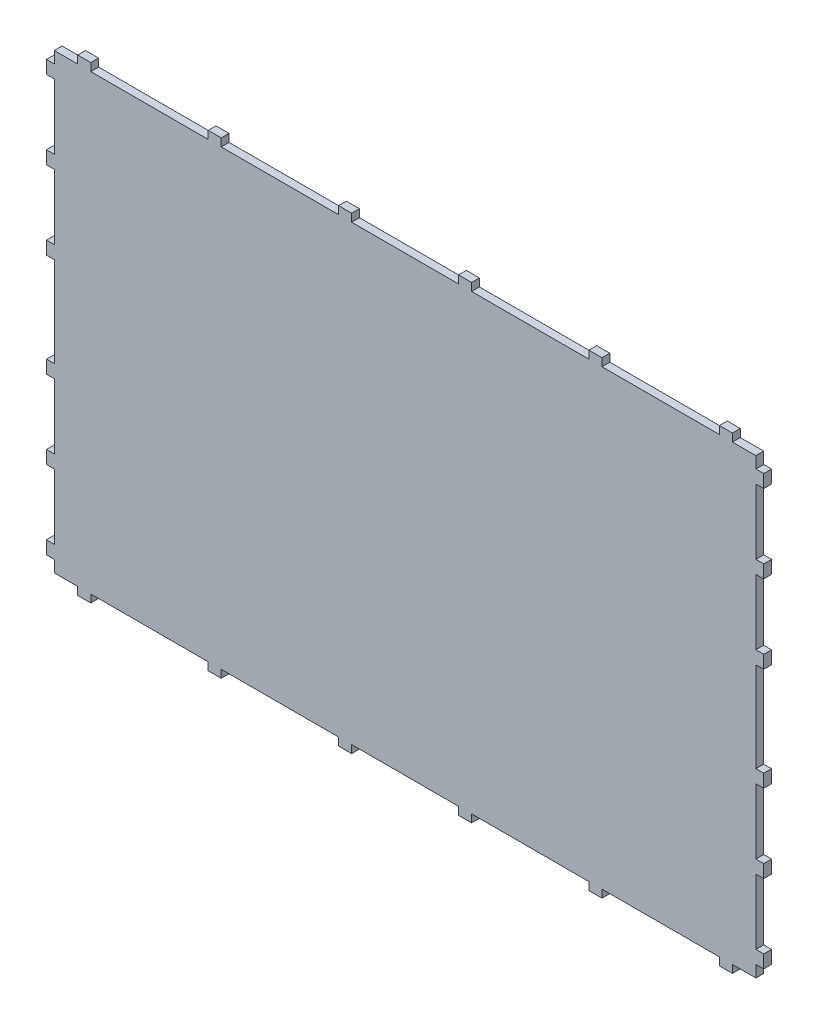
SolidWorks part; units mm, degrees
material "Клен"
ref_plane "Спереди" through (0, 0, 0) normal (0, 0, 1) x (1, 0, 0)
ref_plane "Сверху" through (0, 0, 0) normal (0, 1, 0) x (1, 0, 0)
ref_plane "Справа" through (0, 0, 0) normal (1, 0, 0) x (0, 0, -1)
sketch "Эскиз1" plane through (0, 0, 0) normal (0, 0, 1) x (1, 0, 0)
  line L0 (-367.4727, 191.9298) -> (-349.4727, 191.9298)
  line L1 (-367.4727, 191.9298) -> (-367.4727, 183.0298)
  line L2 (-367.4727, -154.9702) -> (-349.4727, -154.9702)
  line L3 (170.5273, 191.9298) -> (170.5273, 183.0298)
  line L4 (-339.4727, -154.9702) -> (-339.4727, -160.9702) construction
  line L5 (-373.4727, 183.0298) -> (-367.4727, 183.0298)
  line L6 (-373.4727, 183.0298) -> (-373.4727, 173.0298)
  line L7 (-373.4727, 173.0298) -> (-367.4727, 173.0298)
  line L9 (-349.4727, 197.9298) -> (-339.4727, 197.9298)
  line L10 (-349.4727, 197.9298) -> (-349.4727, 191.9298)
  line L12 (-339.4727, 197.9298) -> (-339.4727, 191.9298)
  line L13 (-249.4727, 197.9298) -> (-239.4727, 197.9298)
  line L14 (-249.4727, 197.9298) -> (-249.4727, 191.9298)
  line L16 (-239.4727, 197.9298) -> (-239.4727, 191.9298)
  line L18 (-149.4727, 191.9298) -> (-149.4727, 197.9298)
  line L19 (-149.4727, 197.9298) -> (-139.4727, 197.9298)
  line L20 (-139.4727, 191.9298) -> (-139.4727, 197.9298)
  line L22 (-57.4727, 191.9298) -> (-57.4727, 197.9298)
  line L23 (-57.4727, 197.9298) -> (-47.4727, 197.9298)
  line L24 (-47.4727, 191.9298) -> (-47.4727, 197.9298)
  line L26 (42.5273, 191.9298) -> (42.5273, 197.9298)
  line L27 (42.5273, 197.9298) -> (52.5273, 197.9298)
  line L28 (52.5273, 191.9298) -> (52.5273, 197.9298)
  line L30 (142.5273, 191.9298) -> (142.5273, 197.9298)
  line L31 (142.5273, 197.9298) -> (152.5273, 197.9298)
  line L32 (152.5273, 191.9298) -> (152.5273, 197.9298)
  line L33 (170.5273, 183.0298) -> (176.5273, 183.0298)
  line L35 (170.5273, 173.0298) -> (176.5273, 173.0298)
  line L36 (176.5273, 183.0298) -> (176.5273, 173.0298)
  line L37 (170.5273, 123.0298) -> (176.5273, 123.0298)
  line L39 (170.5273, 113.0298) -> (176.5273, 113.0298)
  line L40 (176.5273, 123.0298) -> (176.5273, 113.0298)
  line L41 (170.5273, 63.0298) -> (176.5273, 63.0298)
  line L43 (170.5273, 53.0298) -> (176.5273, 53.0298)
  line L44 (176.5273, 63.0298) -> (176.5273, 53.0298)
  line L45 (170.5273, -15.9702) -> (176.5273, -15.9702)
  line L47 (170.5273, -25.9702) -> (176.5273, -25.9702)
  line L48 (176.5273, -15.9702) -> (176.5273, -25.9702)
  line L49 (170.5273, -75.9702) -> (176.5273, -75.9702)
  line L51 (170.5273, -85.9702) -> (176.5273, -85.9702)
  line L52 (176.5273, -75.9702) -> (176.5273, -85.9702)
  line L53 (170.5273, -135.9702) -> (176.5273, -135.9702)
  line L55 (170.5273, -145.9702) -> (176.5273, -145.9702)
  line L56 (176.5273, -135.9702) -> (176.5273, -145.9702)
  line L58 (142.5273, -154.9702) -> (142.5273, -160.9702)
  line L59 (142.5273, -160.9702) -> (152.5273, -160.9702)
  line L60 (152.5273, -154.9702) -> (152.5273, -160.9702)
  line L62 (42.5273, -154.9702) -> (42.5273, -160.9702)
  line L63 (42.5273, -160.9702) -> (52.5273, -160.9702)
  line L64 (52.5273, -154.9702) -> (52.5273, -160.9702)
  line L66 (-57.4727, -154.9702) -> (-57.4727, -160.9702)
  line L67 (-57.4727, -160.9702) -> (-47.4727, -160.9702)
  line L68 (-47.4727, -154.9702) -> (-47.4727, -160.9702)
  line L70 (-149.4727, -154.9702) -> (-149.4727, -160.9702)
  line L71 (-149.4727, -160.9702) -> (-139.4727, -160.9702)
  line L72 (-139.4727, -154.9702) -> (-139.4727, -160.9702)
  line L74 (-249.4727, -154.9702) -> (-249.4727, -160.9702)
  line L75 (-249.4727, -160.9702) -> (-239.4727, -160.9702)
  line L76 (-239.4727, -154.9702) -> (-239.4727, -160.9702)
  line L78 (-349.4727, -154.9702) -> (-349.4727, -160.9702)
  line L79 (-349.4727, -160.9702) -> (-339.4727, -160.9702)
  line L80 (-339.4727, -154.9702) -> (-339.4727, -160.9702)
  line L81 (-367.4727, -160.9702) -> (170.5273, -160.9702) construction
  line L82 (-367.4727, 173.0298) -> (-367.4727, 123.0298)
  line L83 (-367.4727, -145.9702) -> (-373.4727, -145.9702)
  line L85 (-367.4727, -135.9702) -> (-373.4727, -135.9702)
  line L86 (-373.4727, -145.9702) -> (-373.4727, -135.9702)
  line L87 (-373.4727, -75.9702) -> (-367.4727, -75.9702)
  line L88 (-373.4727, -75.9702) -> (-373.4727, -85.9702)
  line L89 (-373.4727, -85.9702) -> (-367.4727, -85.9702)
  line L91 (-373.4727, -15.9702) -> (-367.4727, -15.9702)
  line L92 (-373.4727, -15.9702) -> (-373.4727, -25.9702)
  line L93 (-373.4727, -25.9702) -> (-367.4727, -25.9702)
  line L95 (-373.4727, 63.0298) -> (-367.4727, 63.0298)
  line L96 (-373.4727, 63.0298) -> (-373.4727, 53.0298)
  line L97 (-373.4727, 53.0298) -> (-367.4727, 53.0298)
  line L99 (-373.4727, 123.0298) -> (-367.4727, 123.0298)
  line L100 (-373.4727, 123.0298) -> (-373.4727, 113.0298)
  line L101 (-373.4727, 113.0298) -> (-367.4727, 113.0298)
  line L103 (-339.4727, 191.9298) -> (-249.4727, 191.9298)
  line L104 (-239.4727, 191.9298) -> (-149.4727, 191.9298)
  line L105 (-139.4727, 191.9298) -> (-57.4727, 191.9298)
  line L106 (-47.4727, 191.9298) -> (42.5273, 191.9298)
  line L107 (52.5273, 191.9298) -> (142.5273, 191.9298)
  line L108 (152.5273, 191.9298) -> (170.5273, 191.9298)
  line L109 (170.5273, 173.0298) -> (170.5273, 123.0298)
  line L110 (170.5273, 113.0298) -> (170.5273, 63.0298)
  line L111 (170.5273, 53.0298) -> (170.5273, -15.9702)
  line L112 (170.5273, -85.9702) -> (170.5273, -135.9702)
  line L113 (170.5273, -145.9702) -> (170.5273, -154.9702)
  line L114 (152.5273, -154.9702) -> (170.5273, -154.9702)
  line L115 (52.5273, -154.9702) -> (142.5273, -154.9702)
  line L116 (-47.4727, -154.9702) -> (42.5273, -154.9702)
  line L117 (-139.4727, -154.9702) -> (-57.4727, -154.9702)
  line L118 (-239.4727, -154.9702) -> (-149.4727, -154.9702)
  line L119 (-339.4727, -154.9702) -> (-249.4727, -154.9702)
  line L120 (-367.4727, -145.9702) -> (-367.4727, -154.9702)
  line L121 (-367.4727, -85.9702) -> (-367.4727, -135.9702)
  line L122 (-367.4727, -25.9702) -> (-367.4727, -75.9702)
  line L123 (-367.4727, 53.0298) -> (-367.4727, -15.9702)
  line L124 (-367.4727, 113.0298) -> (-367.4727, 63.0298)
  line L125 (170.5273, -25.9702) -> (170.5273, -75.9702)
extrude "Бобышка-Вытянуть1" add sketch "Эскиз1" along normal blind 6
